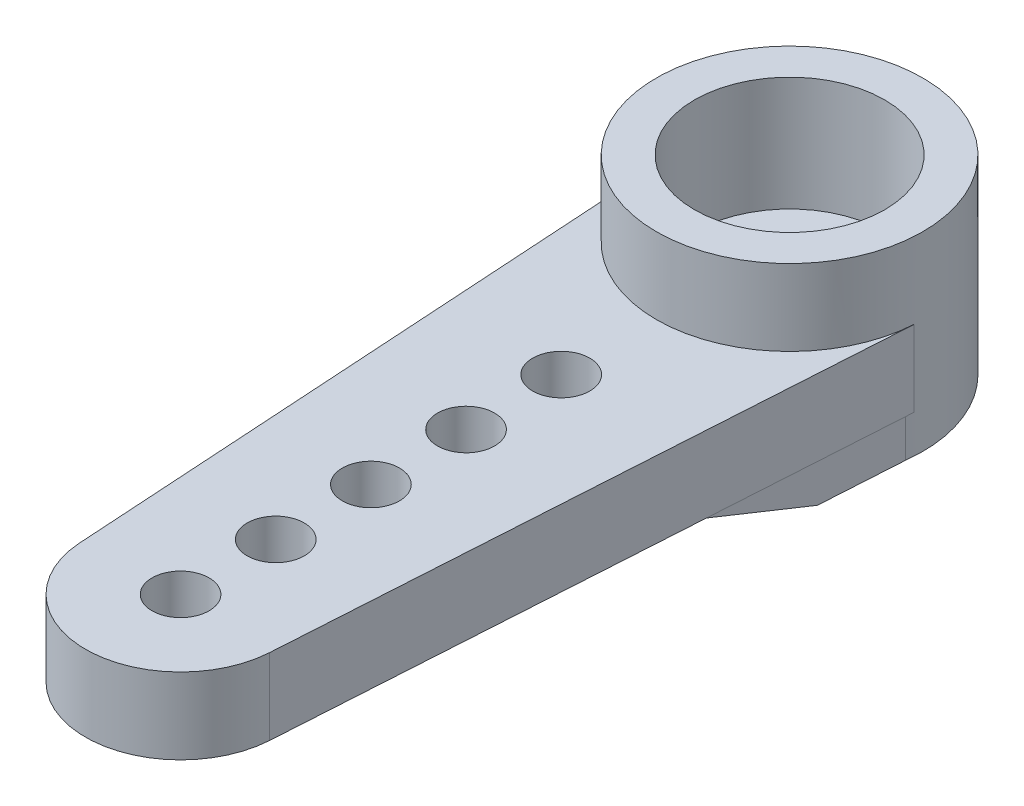
SolidWorks part; units mm, degrees
ref_plane "前视基准面" through (0, 0, 0) normal (0, 0, 1) x (1, 0, 0)
ref_plane "上视基准面" through (0, 0, 0) normal (0, 1, 0) x (1, 0, 0)
ref_plane "右视基准面" through (0, 0, 0) normal (1, 0, 0) x (0, 0, -1)
other "Configuration Table"
sketch "草图1" plane through (0, 0, 0) normal (0, 1, 0) x (1, 0, 0)
  circle A0 centre (0, 0) radius 3.5
  dimension "D1" = 7
extrude "凸台-拉伸1" add sketch "草图1" along normal blind 5
sketch "草图2" plane through (0, 5, 0) normal (0, 1, 0) x (1, 0, 0)
  circle A0 centre (0, 0) radius 2.5
  dimension "D1" = 5
extrude "切除-拉伸1" cut sketch "草图2" against normal blind 3
sketch "草图3" plane through (0, 0, 0) normal (0, -1, 0) x (1, 0, 0)
  circle A0 centre (0, 0) radius 2.5
  dimension "D1" = 5
extrude "切除-拉伸2" cut sketch "草图3" against normal blind 1.5
sketch "草图4" plane through (0, 1.5, 0) normal (0, -1, 0) x (1, 0, 0)
  circle A0 centre (0, 0) radius 1.25
  dimension "D1" = 2.5
extrude "切除-拉伸3" cut sketch "草图4" against normal blind 1.5
sketch "草图5" plane through (0, 5, 0) normal (0, 1, 0) x (1, 0, 0)
  line L0 (0, 0) -> (0, -25.1141) construction
  line L1 (3.7389, 3.7052) -> (1.8782, -26.008)
  line L2 (-3.6428, 2.1716) -> (-1.926, -25.2449)
  circle A0 centre (0, -16) radius 2.5
  circle A1 centre (0, 0) radius 3.5 construction
  circle A2 centre (0, 0) radius 3.5
  circle A3 centre (0, -16) radius 0.75
  circle A4 centre (0, -13.5) radius 0.75
  circle A5 centre (0, -11) radius 0.75
  circle A6 centre (0, -8.5) radius 0.75
  circle A7 centre (0, -6) radius 0.75
  circle M5 centre (0, 0) radius 3.5
  dimension "D1" = 5
  dimension "D2" = 16
  dimension "D3" = 1.5
  dimension "D4" = 1.5
  dimension "D5" = 1.5
  dimension "D6" = 1.5
  dimension "D7" = 1.5
  dimension "D8" = 2.5
  dimension "D9" = 2.5
  dimension "D10" = 2.5
  dimension "D11" = 2.5
extrude "凸台-拉伸2" add sketch "草图5" against normal blind 2 from offset 2 contours L0 A4 A0 A3 | L0 L2 A0 A4 A5 A6 A7 M5 | A2 L0 A7 A6 A5 A4 A0 L1 | A4 L0 A3 A0 region at (1.7229, 5, 8.1142) region at (-1.7229, 5, 8.1142) region at (-1.1749, 5, 16.105) region at (1.1749, 5, 16.105) offset against normal yes
sketch "草图6" plane through (0, 0, 0) normal (1, 0, 0) x (0, 0, -1)
  line L0 (-5.3562, 1) -> (-3.6241, 0)
  line L1 (-0.2188, 1) -> (-16.1562, 1) construction
  line L2 (-6.75, 1) -> (-5.25, 1) construction
  line L3 (-3.6241, 0) -> (-3.1241, 0)
  line L4 (-3.5, 0) -> (3.5, 0) construction
  line L5 (-3.1241, 0) -> (-3.1241, 1)
  line L6 (-3.1241, 1) -> (-5.3562, 1)
  dimension "D1" = 0.5
  dimension "D2" = 30
extrude "凸台-拉伸3" add sketch "草图6" along normal mid plane 1
sketch "草图7" plane through (0, 1, 0) normal (0, -1, 0) x (1, 0, 0)
  line L0 (0, 5.3562) -> (-3.1714, 5.3562) construction
  line L1 (0.3847, 5.3562) -> (-0.3847, 5.3562) construction
  line L2 (-3.4932, 0.2188) -> (-2.4951, 16.1562) construction
  line L3 (0, 5.3562) -> (3.1714, 5.3562) construction
  line L4 (3.4932, 0.2187) -> (2.4951, 16.1562) construction
  line L5 (3.5, 0) -> (3.1714, 5.3562)
  line L6 (3.5, 0) -> (2.8, 0)
  line L7 (2.8, 0) -> (2.4714, 5.3562)
  line L8 (2.4714, 5.3562) -> (3.1714, 5.3562)
  line L9 (-3.5, 0) -> (-3.1714, 5.3562)
  line L10 (-3.1714, 5.3562) -> (-2.4714, 5.3562)
  line L11 (-2.4714, 5.3562) -> (-2.8, 0)
  line L12 (-2.8, 0) -> (-3.5, 0)
  arc A0 (-0.5, 3.4641) -> (0.5, 3.4641) centre (0, 0) ccw construction
  dimension "D1" = 0.7
  dimension "D2" = 0.7
extrude "凸台-拉伸4" add sketch "草图7" along normal blind 1
chamfer "倒角1" distance 1 angle 70 2 edges at (2.8214, 0, 5.3562) (-2.8214, 0, 5.3562) first distance on face at (2.8214, 0.5, 5.3562) first distance on face at (-2.8214, 0.5, 5.3562)
